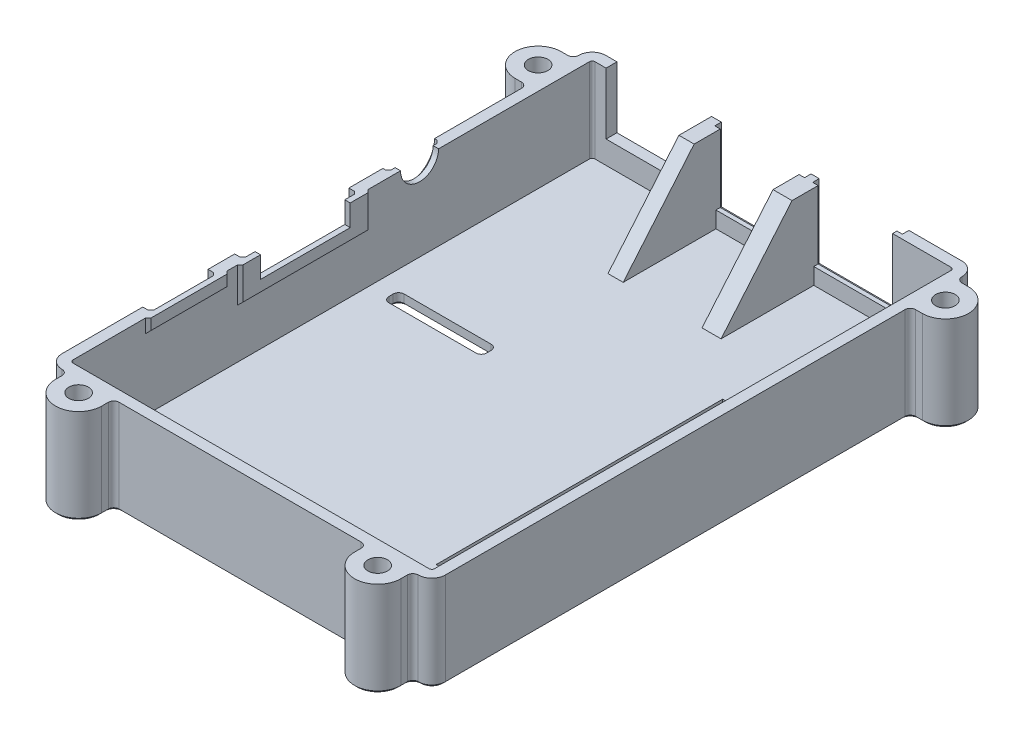
SolidWorks part; units mm, degrees
ref_plane "Front Plane" through (0, 0, 0) normal (0, 0, 1) x (1, 0, 0)
ref_plane "Top Plane" through (0, 0, 0) normal (0, 1, 0) x (1, 0, 0)
ref_plane "Right Plane" through (0, 0, 0) normal (1, 0, 0) x (0, 0, -1)
sketch "Sketch2" plane through (0, 0, 0) normal (0, 1, 0) x (1, 0, 0)
  line L1 (2.5, 0) -> (68, 0)
  line L2 (0, 2.5) -> (0, 97.5)
  line L3 (2.5, 100) -> (68, 100)
  line L4 (70.5, 2.5) -> (70.5, 97.5)
  arc A0 (0, 2.5) -> (2.5, 0) centre (2.5, 2.5) ccw
  arc A1 (68, 0) -> (70.5, 2.5) centre (68, 2.5) ccw
  arc A2 (70.5, 97.5) -> (68, 100) centre (68, 97.5) ccw
  arc A3 (2.5, 100) -> (0, 97.5) centre (2.5, 97.5) ccw
  point P7 (0, 0)
  point P10 (70.5, 0)
  point P13 (70.5, 100)
  point P16 (0, 100)
  dimension "D3" = 2.5
  dimension "D1" = 70.5
  dimension "D2" = 100
extrude "Base" add sketch "Sketch2" along normal blind 17.5
shell "Shell" thickness 2 removed face at (35.25, 17.5, -50)
sketch "Sketch14" plane through (0, 0, 0) normal (0, -1, 0) x (1, 0, 0)
  line L0 (35.25, 0) -> (35.25, -100) construction
  line L2 (68, -100) -> (2.5, -100) construction
  line L3 (-2.2, -88) -> (0, -88)
  line L4 (0, -97.5) -> (0, -2.5) construction
  line L5 (0, -88) -> (0, -96.5)
  line L6 (0, -96.5) -> (-2.2, -96.5)
  line L7 (3.5, 2.2) -> (3.5, 0)
  line L8 (2.5, 0) -> (68, 0) construction
  line L9 (3.5, 0) -> (12, 0)
  line L10 (12, 0) -> (12, 2.2)
  line L11 (72.7, -88) -> (70.5, -88)
  line L12 (70.5, -96.5) -> (72.7, -96.5)
  line L13 (70.5, -88) -> (70.5, -96.5)
  line L14 (58.5, 0) -> (58.5, 2.2)
  line L15 (67, 0) -> (58.5, 0)
  line L16 (67, 2.2) -> (67, 0)
  line L17 (2.5, 0) -> (68, 0) construction
  arc A0 (-2.2, -88) -> (-2.2, -96.5) centre (-2.2, -92.25) ccw
  arc A1 (3.5, 2.2) -> (12, 2.2) centre (7.75, 2.2) cw
  arc A2 (72.7, -88) -> (72.7, -96.5) centre (72.7, -92.25) cw
  arc A3 (67, 2.2) -> (58.5, 2.2) centre (62.75, 2.2) ccw
  dimension "D1" = 2.2
  dimension "D2" = 8.5
  dimension "D3" = 3.5
  dimension "D4" = 3.5
extrude "Clamps" add sketch "Sketch14" against normal up to surface (17.5 mm away) up to face at (35.25, 17.5, -50)
fillet "Clamp Fillets" radius 1 8 edges at (58.5, 8.75, 0) (67, 8.75, 0) (12, 8.75, 0) (3.5, 8.75, 0) (0, 8.75, -96.5) (0, 8.75, -88) (70.5, 8.75, -88) (70.5, 8.75, -96.5)
sketch "Sketch20" plane through (0, 0, 0) normal (0, -1, 0) x (1, 0, 0)
  circle A0 centre (7.75, 2.2) radius 1.8
  circle A1 centre (62.75, 2.2) radius 1.8
  circle A2 centre (72.7, -92.25) radius 1.8
  circle A3 centre (-2.2, -92.25) radius 1.8
  arc A4 (12, 2.2) -> (3.5, 2.2) centre (7.75, 2.2) ccw construction
  arc A5 (67, 2.2) -> (58.5, 2.2) centre (62.75, 2.2) ccw construction
  arc A6 (-2.2, -88) -> (-2.2, -96.5) centre (-2.2, -92.25) ccw construction
  arc A7 (72.7, -96.5) -> (72.7, -88) centre (72.7, -92.25) ccw construction
  dimension "D1" = 3.6
extrude "Clamp Holes" cut sketch "Sketch20" against normal through all
sketch "Sketch21" plane through (0, 0, 0) normal (0, -1, 0) x (1, 0, 0)
  circle A0 centre (7.75, 2.2) radius 2.9
  circle A1 centre (62.75, 2.2) radius 2.9
  circle A2 centre (72.7, -92.25) radius 2.9
  circle A3 centre (-2.2, -92.25) radius 2.9
  circle A4 centre (-2.2, -92.25) radius 1.8 construction
  circle A5 centre (7.75, 2.2) radius 1.8 construction
  circle A6 centre (62.75, 2.2) radius 1.8 construction
  circle A7 centre (72.7, -92.25) radius 1.8 construction
  dimension "D1" = 5.8
extrude "Clamp Countersinks" cut sketch "Sketch21" against normal blind 3.4
chamfer "Clamp Countersink Chamfers" distance 0.3 angle 45 4 edges at (-2.2, 0, -95.15) (72.7, 0, -95.15) (62.75, 0, -0.7) (7.75, 0, -0.7)
sketch "Sketch24" plane through (0, 0, -100) normal (0, 0, -1) x (-1, 0, 0)
  line L0 (-68, 17.5) -> (-2.5, 17.5) construction
  line L1 (-57.25, 17.5) -> (-42.75, 17.5)
  line L2 (-57.25, 17.5) -> (-57.25, 5)
  line L3 (-57.25, 5) -> (-42.75, 5)
  line L4 (-42.75, 17.5) -> (-42.75, 5)
  line L6 (0, 17.5) -> (0, 0) construction
  line L7 (-39.25, 17.5) -> (-24.75, 17.5)
  line L8 (-39.25, 17.5) -> (-39.25, 5)
  line L9 (-39.25, 5) -> (-24.75, 5)
  line L10 (-24.75, 17.5) -> (-24.75, 5)
  dimension "D1" = 14.5
  dimension "D2" = 24.75
  dimension "D3" = 42.75
  dimension "D4" = 12.5
extrude "USB Cutout" cut sketch "Sketch24" against normal blind 18.25
sketch "Sketch25" plane through (0, 0, -100) normal (0, 0, -1) x (-1, 0, 0)
  line L0 (-42.75, 17.5) -> (-39.25, 17.5) construction
  line L1 (-41.75, 17.5) -> (-58.25, 17.5)
  line L2 (-41.75, 17.5) -> (-41.75, 4)
  line L3 (-41.75, 4) -> (-58.25, 4)
  line L4 (-58.25, 17.5) -> (-58.25, 4)
  line L6 (-24.75, 17.5) -> (-2.5, 17.5) construction
  line L7 (-23.75, 17.5) -> (-40.25, 17.5)
  line L8 (-23.75, 17.5) -> (-23.75, 4)
  line L9 (-23.75, 4) -> (-40.25, 4)
  line L10 (-40.25, 17.5) -> (-40.25, 4)
  line L12 (-57.25, 17.5) -> (-57.25, 5) construction
  line L13 (-42.75, 5) -> (-42.75, 17.5) construction
  line L14 (-39.25, 17.5) -> (-39.25, 5) construction
  line L15 (-24.75, 5) -> (-24.75, 17.5) construction
  point P18 (-57.25, 11.25)
  dimension "D1" = 1
  dimension "D2" = 1
  dimension "D3" = 1
  dimension "D4" = 1
  dimension "D5" = 13.5
extrude "USB Approach" cut sketch "Sketch25" against normal blind 1.2
sketch "Sketch26" plane through (42.75, 0, 0) normal (1, 0, 0) x (0, 0, -1)
  line L0 (98, 2) -> (98, 17.5)
  line L1 (98, 17.5) -> (94, 17.5)
  line L2 (98, 2) -> (80.95, 2)
  line L3 (80.95, 2) -> (94, 17.5)
  line L4 (100, 4) -> (100, 17.5) construction
  line L5 (100, 4) -> (100, 17.5) construction
  dimension "D1" = 6
  dimension "D2" = 19.05
extrude "USB Inner Support" add sketch "Sketch26" against normal up to surface (3.5 mm away) up to face at (39.25, 11.25, -98.4)
sketch "Sketch27" plane through (24.75, 0, 0) normal (1, 0, 0) x (0, 0, -1)
  line L0 (98, 2) -> (98, 17.5)
  line L1 (98, 17.5) -> (94, 17.5)
  line L2 (98, 2) -> (80.95, 2)
  line L3 (80.95, 2) -> (94, 17.5)
  line L4 (100, 4) -> (100, 17.5) construction
  line L5 (100, 4) -> (100, 17.5) construction
  dimension "D1" = 6
  dimension "D2" = 19.05
extrude "USB Outer Support" add sketch "Sketch27" against normal blind 2.8
sketch "Sketch28" plane through (0, 0, -100) normal (0, 0, -1) x (-1, 0, 0)
  line L0 (-23.75, 17.5) -> (-2.5, 17.5) construction
  line L1 (-21.95, 17.5) -> (-4.55, 17.5)
  line L2 (-21.95, 17.5) -> (-21.95, 6.2)
  line L3 (-21.95, 6.2) -> (-4.55, 6.2)
  line L4 (-4.55, 17.5) -> (-4.55, 6.2)
  line L5 (0, 17.5) -> (0, 0) construction
  dimension "D1" = 17.4
  dimension "D2" = 4.55
  dimension "D3" = 11.3
extrude "RJ45 Cutout" cut sketch "Sketch28" against normal blind 22.7
sketch "Sketch29" plane through (2, 0, 0) normal (1, 0, 0) x (0, 0, -1)
  line L0 (97.5, 17.5) -> (2.5, 17.5) construction
  line L1 (15.85, 17.5) -> (30.85, 17.5)
  line L2 (15.85, 17.5) -> (15.85, 15)
  line L3 (15.85, 15) -> (30.85, 15)
  line L4 (30.85, 17.5) -> (30.85, 15)
  line L5 (0, 17.5) -> (0, 0) construction
  line L6 (32.75, 17.5) -> (56.75, 17.5)
  line L7 (32.75, 17.5) -> (32.75, 11.07)
  line L8 (32.75, 11.07) -> (56.75, 11.07)
  line L9 (56.75, 17.5) -> (56.75, 11.07)
  dimension "D1" = 24
  dimension "D2" = 15
  dimension "D3" = 15.85
  dimension "D4" = 32.75
  dimension "D5" = 2.5
  dimension "D6" = 6.43
extrude "HDMI Support" add sketch "Sketch29" along normal blind 0.5
chamfer "HDMI Support Chamfer" distance 0.5 angle 45 6 edges at (2.5, 14.285, -56.75) (2.5, 11.07, -44.75) (2.5, 14.285, -32.75) (2.5, 16.25, -30.85) (2.5, 15, -23.35) (2.5, 16.25, -15.85)
sketch "Sketch30" plane through (0, 0, 0) normal (-1, 0, 0) x (0, 0, 1)
  line L0 (-87, 17.5) -> (-2.5, 17.5) construction
  line L1 (-34.25, 17.5) -> (-55.25, 17.5)
  line L2 (-34.25, 17.5) -> (-34.25, 11.57)
  line L3 (-34.25, 11.57) -> (-55.25, 11.57)
  line L4 (-55.25, 17.5) -> (-55.25, 11.57)
  line L5 (0, 17.5) -> (0, 0) construction
  line L6 (-29.35, 17.5) -> (-17.35, 17.5)
  line L7 (-29.35, 17.5) -> (-29.35, 15.5)
  line L8 (-29.35, 15.5) -> (-17.35, 15.5)
  line L9 (-17.35, 17.5) -> (-17.35, 15.5)
  dimension "D1" = 12
  dimension "D2" = 21
  dimension "D3" = 17.35
  dimension "D4" = 34.25
  dimension "D5" = 5.93
  dimension "D6" = 2
extrude "HDMI Approach" cut sketch "Sketch30" against normal blind 1.5
sketch "Sketch31" plane through (1.5, 0, 0) normal (-1, 0, 0) x (0, 0, 1)
  line L0 (-34.25, 17.5) -> (-55.25, 17.5) construction
  line L1 (-53, 17.5) -> (-36.5, 17.5)
  line L2 (-53, 17.5) -> (-53, 13.57)
  line L3 (-53, 13.57) -> (-36.5, 13.57)
  line L4 (-36.5, 17.5) -> (-36.5, 13.57)
  line L5 (-55.25, 17.5) -> (-55.25, 11.57) construction
  line L6 (-34.25, 11.57) -> (-34.25, 17.5) construction
  line L7 (-55.25, 11.57) -> (-34.25, 11.57) construction
  dimension "D1" = 2.25
  dimension "D2" = 2.25
  dimension "D3" = 2
extrude "HDMI Cutout" cut sketch "Sketch31" against normal blind 1
chamfer "HDMI Approach Chamfer" distance 0.5 angle 45 6 edges at (1.5, 16.5, -17.35) (1.5, 15.5, -23.35) (1.5, 16.5, -29.35) (1.5, 14.535, -34.25) (1.5, 11.57, -44.75) (1.5, 14.535, -55.25)
sketch "Sketch32" plane through (0, 0, 0) normal (-1, 0, 0) x (0, 0, 1)
  line L0 (-87, 17.5) -> (-55.25, 17.5) construction
  line L1 (0, 17.5) -> (0, 0) construction
  circle A0 centre (-66.25, 17.5) radius 3.5
  dimension "D1" = 7
  dimension "D2" = 66.25
extrude "Audio Cutout" cut sketch "Sketch32" against normal blind 2
sketch "Sketch33" plane through (0, 0, 0) normal (-1, 0, 0) x (0, 0, 1)
  circle A0 centre (-66.25, 17.5) radius 4.75
  arc A1 (-69.75, 17.5) -> (-62.75, 17.5) centre (-66.25, 17.5) ccw construction
  dimension "D1" = 9.5
extrude "Audio Approach" cut sketch "Sketch33" against normal blind 1
chamfer "Audio Approach Chamfer" distance 0.5 angle 45 1 edges at (1, 12.75, -66.25)
sketch "Sketch34" plane through (0, 0, 0) normal (0, -1, 0) x (1, 0, 0)
  line L0 (70.5, -2.5) -> (70.5, -87) construction
  line L1 (52.5, -18.8) -> (58.5, -18.8)
  line L2 (52.5, -18.8) -> (52.5, -71.5)
  line L3 (52.5, -71.5) -> (58.5, -71.5)
  line L4 (58.5, -18.8) -> (58.5, -71.5)
  line L5 (13, 0) -> (57.5, 0) construction
  point P6 (55.5, -18.8)
  dimension "D1" = 6
  dimension "D2" = 52.7
  dimension "D3" = 12
  dimension "D4" = 18.8
extrude "Header Cutout" cut sketch "Sketch34" against normal blind 2
sketch "Sketch35" plane through (0, 0, 0) normal (0, -1, 0) x (1, 0, 0)
  line L0 (55.5, -18.8) -> (55.5, -71.5) construction
  line L1 (58.5, -18.8) -> (52.5, -18.8) construction
  line L2 (52.5, -71.5) -> (58.5, -71.5) construction
  line L3 (52.5, -45.15) -> (58.5, -45.15) construction
  line L4 (52.5, -18.8) -> (52.5, -71.5) construction
  line L5 (58.5, -71.5) -> (58.5, -18.8) construction
  line L6 (56, -18.8) -> (55, -18.8)
  line L7 (55, -18.8) -> (55, -19.8)
  line L8 (55, -19.8) -> (53.5, -19.8)
  line L9 (53.5, -19.8) -> (53.5, -24.7625)
  line L10 (53.5, -24.7625) -> (52.5, -24.7625)
  line L11 (52.5, -24.7625) -> (52.5, -25.7625)
  line L12 (52.5, -25.7625) -> (53.5, -25.7625)
  line L13 (53.5, -25.7625) -> (53.5, -37.6875)
  line L14 (53.5, -37.6875) -> (52.5, -37.6875)
  line L15 (52.5, -37.6875) -> (52.5, -38.6875)
  line L16 (52.5, -38.6875) -> (53.5, -38.6875)
  line L17 (53.5, -38.6875) -> (53.5, -43.65)
  line L18 (53.5, -43.65) -> (55, -43.65)
  line L19 (55, -43.65) -> (55, -44.65)
  line L20 (55, -44.65) -> (52.5, -44.65)
  line L21 (52.5, -44.65) -> (52.5, -45.65)
  line L22 (56, -71.5) -> (55, -71.5)
  line L23 (55, -45.65) -> (52.5, -45.65)
  line L24 (55, -46.65) -> (55, -45.65)
  line L25 (53.5, -46.65) -> (55, -46.65)
  line L26 (53.5, -51.6125) -> (53.5, -46.65)
  line L27 (52.5, -51.6125) -> (53.5, -51.6125)
  line L28 (52.5, -52.6125) -> (52.5, -51.6125)
  line L29 (53.5, -52.6125) -> (52.5, -52.6125)
  line L30 (53.5, -64.5375) -> (53.5, -52.6125)
  line L31 (52.5, -64.5375) -> (53.5, -64.5375)
  line L32 (52.5, -65.5375) -> (52.5, -64.5375)
  line L33 (53.5, -65.5375) -> (52.5, -65.5375)
  line L34 (53.5, -70.5) -> (53.5, -65.5375)
  line L35 (55, -70.5) -> (53.5, -70.5)
  line L36 (55, -71.5) -> (55, -70.5)
  line L37 (56, -71.5) -> (56, -70.5)
  line L38 (56, -70.5) -> (57.5, -70.5)
  line L39 (57.5, -70.5) -> (57.5, -65.5375)
  line L40 (57.5, -65.5375) -> (58.5, -65.5375)
  line L41 (58.5, -65.5375) -> (58.5, -64.5375)
  line L42 (58.5, -64.5375) -> (57.5, -64.5375)
  line L43 (57.5, -64.5375) -> (57.5, -52.6125)
  line L44 (57.5, -52.6125) -> (58.5, -52.6125)
  line L45 (58.5, -52.6125) -> (58.5, -51.6125)
  line L46 (58.5, -51.6125) -> (57.5, -51.6125)
  line L47 (57.5, -51.6125) -> (57.5, -46.65)
  line L48 (57.5, -46.65) -> (56, -46.65)
  line L49 (56, -46.65) -> (56, -45.65)
  line L50 (56, -45.65) -> (58.5, -45.65)
  line L51 (58.5, -44.65) -> (58.5, -45.65)
  line L52 (56, -44.65) -> (58.5, -44.65)
  line L53 (56, -43.65) -> (56, -44.65)
  line L54 (57.5, -43.65) -> (56, -43.65)
  line L55 (57.5, -38.6875) -> (57.5, -43.65)
  line L56 (58.5, -38.6875) -> (57.5, -38.6875)
  line L57 (58.5, -37.6875) -> (58.5, -38.6875)
  line L58 (57.5, -37.6875) -> (58.5, -37.6875)
  line L59 (57.5, -25.7625) -> (57.5, -37.6875)
  line L60 (58.5, -25.7625) -> (57.5, -25.7625)
  line L61 (58.5, -24.7625) -> (58.5, -25.7625)
  line L62 (57.5, -24.7625) -> (58.5, -24.7625)
  line L63 (57.5, -19.8) -> (57.5, -24.7625)
  line L64 (56, -19.8) -> (57.5, -19.8)
  line L65 (56, -18.8) -> (56, -19.8)
  dimension "D1" = 0.5
  dimension "D2" = 1
  dimension "D3" = 1.5
  dimension "D4" = 11.925
extrude "Header Cover" add sketch "Sketch35" against normal blind 1
chamfer "Shell Chamfer" distance 0.5 angle 45 44 edges at (53.75, 0, -71.5) (52.5, 0, -68.5187) (52.5, 0, -58.575) (52.5, 0, -48.6313) (52.5, 0, -41.6688) (52.5, 0, -31.725) (52.5, 0, -21.7813) (53.75, 0, -18.8) (57.25, 0, -18.8) (58.5, 0, -21.7813) (58.5, 0, -31.725) (58.5, 0, -41.6688) (58.5, 0, -48.6313) (58.5, 0, -58.575) (58.5, 0, -68.5187) (57.25, 0, -71.5) (69.7678, 0, -99.2678) (70.7929, 0, -96.7929) (72.1, 0, -96.5) (76.95, 0, -92.25) (72.1, 0, -88) (70.7929, 0, -87.7071) (70.5, 0, -44.75) (35.25, 0, -100) (0.7322, 0, -99.2678) (-0.2929, 0, -96.7929) (-1.6, 0, -96.5) (-6.45, 0, -92.25) (-1.6, 0, -88) (0, 0, -44.75) (69.7678, 0, -0.7322) (67.2929, 0, 0.2929) (67, 0, 1.6) (62.75, 0, 6.45) (58.5, 0, 1.6) (58.2071, 0, 0.2929) (0.7322, 0, -0.7322) (3.5, 0, 1.6) (7.75, 0, 6.45) (12, 0, 1.6) (12.2929, 0, 0.2929) (35.25, 0, 0) (-0.2929, 0, -87.7071) (3.2071, 0, 0.2929)
sketch "Sketch38" plane through (0, 0, 0) normal (0, -1, 0) x (1, 0, 0)
  line L0 (68, -100) -> (2.5, -100) construction
  line L1 (6.45, -56.157) -> (22.45, -56.157)
  line L2 (5.45, -57.157) -> (5.45, -57.957)
  line L3 (6.45, -58.957) -> (22.45, -58.957)
  line L4 (23.45, -57.157) -> (23.45, -57.957)
  line L5 (0, -87) -> (0, -2.5) construction
  arc A0 (22.45, -56.157) -> (23.45, -57.157) centre (22.45, -57.157) cw
  arc A1 (23.45, -57.957) -> (22.45, -58.957) centre (22.45, -57.957) cw
  arc A2 (6.45, -58.957) -> (5.45, -57.957) centre (6.45, -57.957) cw
  arc A3 (5.45, -57.157) -> (6.45, -56.157) centre (6.45, -57.157) cw
  point P12 (23.45, -58.957)
  point P15 (5.45, -58.957)
  point P18 (5.45, -56.157)
  dimension "D5" = 1
  dimension "D1" = 18
  dimension "D2" = 2.8
  dimension "D3" = 41.043
  dimension "D4" = 5.45
extrude "Ribbon Slot" cut sketch "Sketch38" against normal up to surface (2 mm away) up to face at (55.5, 2, -45.15)
chamfer "Ribbon Slot Chamfer" distance 0.5 angle 45 8 edges at (14.45, 0, -56.157) (23.1571, 0, -56.4499) (23.45, 0, -57.557) (23.1571, 0, -58.6641) (14.45, 0, -58.957) (5.7429, 0, -58.6641) (5.45, 0, -57.557) (5.7429, 0, -56.4499)
